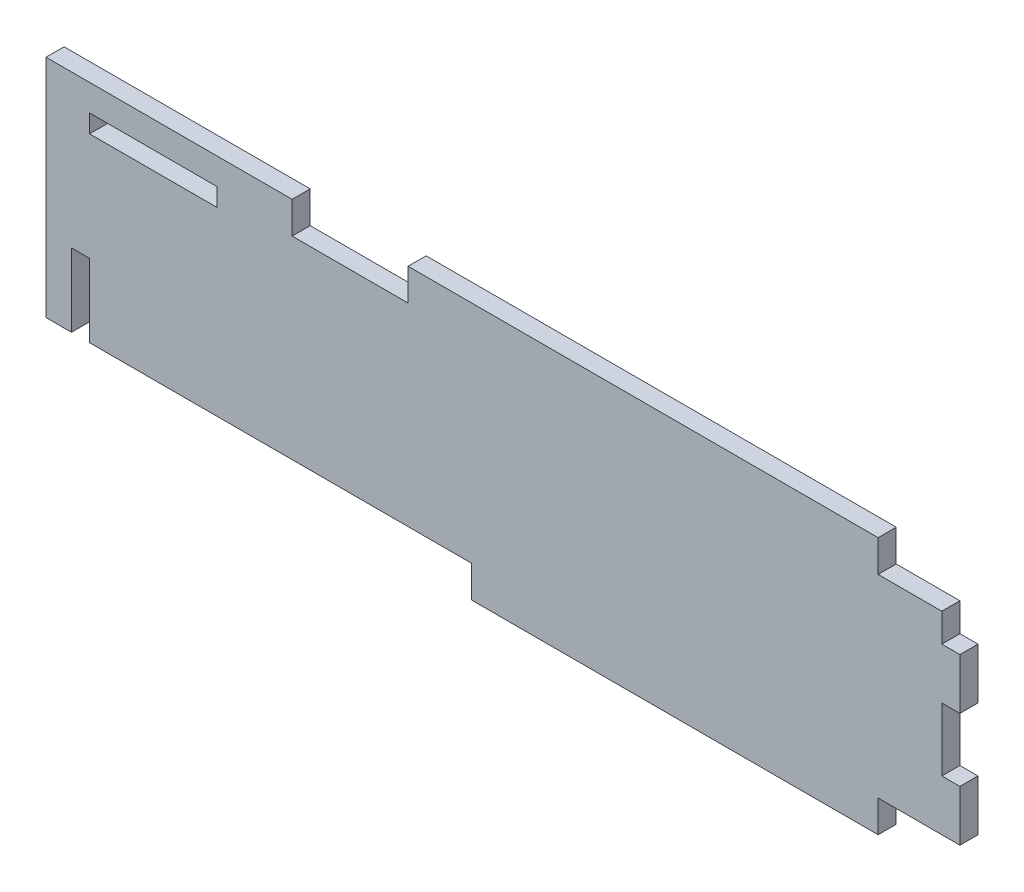
SolidWorks part; units mm, degrees
ref_plane "Front Plane" through (0, 0, 0) normal (0, 0, 1) x (1, 0, 0)
ref_plane "Top Plane" through (0, 0, 0) normal (0, 1, 0) x (1, 0, 0)
ref_plane "Right Plane" through (0, 0, 0) normal (1, 0, 0) x (0, 0, -1)
sketch "Sketch1" plane through (0, 0, 0) normal (0, 0, 1) x (1, 0, 0)
  line L0 (-6.35, 4.7244) -> (1.8034, 4.7244) construction
  line L1 (-6.35, 4.7244) -> (-6.35, 1.5494) construction
  line L2 (-6.35, 1.5494) -> (-46.863, 1.5494) construction
  line L3 (-46.863, 1.5494) -> (-46.863, 4.7244) construction
  line L4 (-84.963, 24.5618) -> (-84.963, 22.7584) construction
  line L5 (-84.963, 22.7584) -> (-72.263, 22.7584) construction
  line L6 (-72.263, 22.7584) -> (-72.263, 24.5618) construction
  line L8 (-72.263, 24.5618) -> (-84.963, 24.5618) construction
  line L10 (-84.963, 24.5618) -> (-84.963, 22.7584)
  line L12 (-84.963, 22.7584) -> (-72.263, 22.7584)
  line L13 (-72.263, 22.7584) -> (-72.263, 24.5618)
  line L14 (-6.35, 27.2034) -> (-53.213, 27.2034) construction
  line L15 (-6.35, 24.0284) -> (-6.35, 27.2034) construction
  line L16 (0, 24.0284) -> (-6.35, 24.0284) construction
  line L17 (0, 24.0284) -> (0, 21.1836) construction
  line L18 (1.8034, 21.1836) -> (0, 21.1836) construction
  line L19 (1.8034, 21.1836) -> (1.8034, 16.1036) construction
  line L20 (1.8034, 16.1036) -> (0, 16.1036) construction
  line L21 (0, 16.1036) -> (0, 9.8044) construction
  line L22 (1.8034, 9.8044) -> (0, 9.8044) construction
  line L23 (1.8034, 9.8044) -> (1.8034, 4.7244) construction
  line L24 (-6.35, 4.7244) -> (1.8034, 4.7244)
  line L25 (-6.35, 4.7244) -> (-6.35, 1.5494)
  line L26 (-6.35, 1.5494) -> (-46.863, 1.5494)
  line L27 (-46.863, 1.5494) -> (-46.863, 4.7244)
  line L28 (-84.963, 4.7244) -> (-46.863, 4.7244)
  line L29 (-89.3064, 15.9639) -> (-89.3064, 4.7244)
  line L30 (-89.3064, 4.7244) -> (-86.7664, 4.7244)
  line L32 (-86.7664, 4.7244) -> (-86.7664, 12.0142)
  line L33 (-64.77, 24.0284) -> (-53.213, 24.0284)
  line L34 (-86.7664, 12.0142) -> (-84.963, 12.0142)
  line L35 (-84.963, 12.0142) -> (-84.963, 4.7244)
  line L36 (-72.263, 24.5618) -> (-84.963, 24.5618)
  line L37 (-53.213, 27.2034) -> (-53.213, 24.0284)
  line L38 (-6.35, 27.2034) -> (-53.213, 27.2034)
  line L39 (-6.35, 24.0284) -> (-6.35, 27.2034)
  line L40 (0, 24.0284) -> (-6.35, 24.0284)
  line L41 (0, 24.0284) -> (0, 21.1836)
  line L42 (1.8034, 21.1836) -> (0, 21.1836)
  line L43 (1.8034, 21.1836) -> (1.8034, 16.1036)
  line L44 (1.8034, 16.1036) -> (0, 16.1036)
  line L45 (0, 16.1036) -> (0, 9.8044)
  line L46 (1.8034, 9.8044) -> (0, 9.8044)
  line L47 (1.8034, 9.8044) -> (1.8034, 4.7244)
  line L48 (-89.3064, 4.7244) -> (-89.3064, 27.2034) construction
  line L49 (-89.3064, 27.2034) -> (-64.77, 27.2034) construction
  line L50 (-64.77, 27.2034) -> (-64.77, 24.0284) construction
  line L51 (-89.3064, 4.7244) -> (-89.3064, 27.2034)
  line L52 (-89.3064, 27.2034) -> (-64.77, 27.2034)
  line L53 (-64.77, 27.2034) -> (-64.77, 24.0284)
extrude "Boss-Extrude1" add sketch "Sketch1" along normal blind 1.8034 contours L47 L46 L45 L44 L43 L42 L41 L40 L39 L38 L37 L29 L30 L32 L34 L28 L27 L26 L25 L24 region at (-42.6327, 14.8336, 0)
